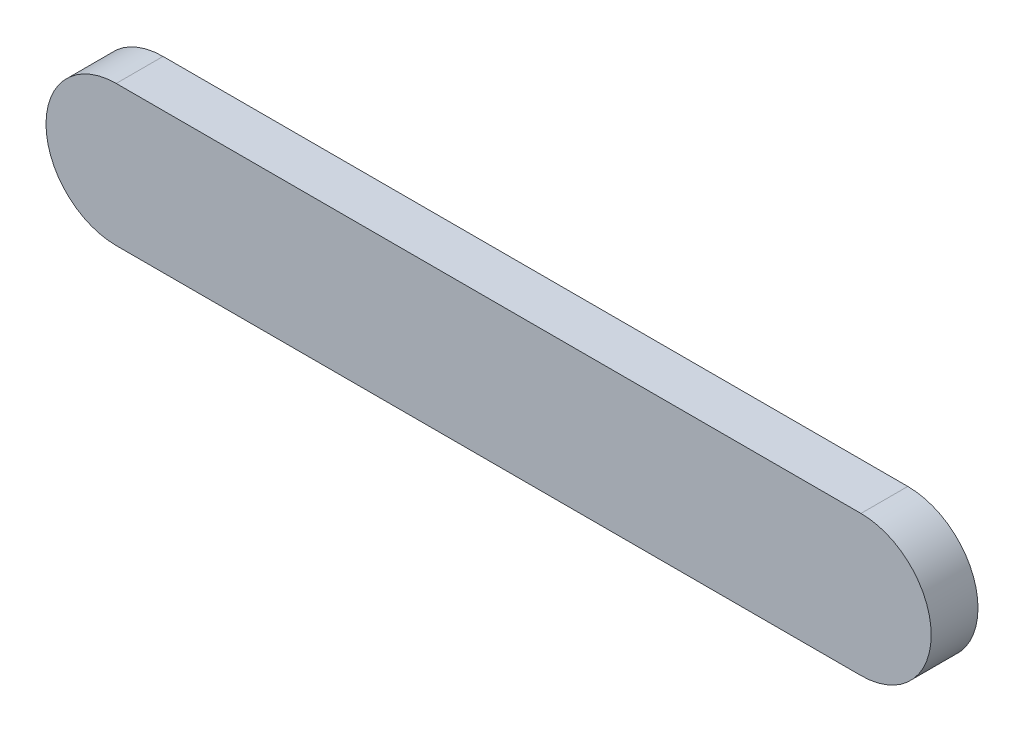
SolidWorks part; units mm, degrees
ref_plane "前视基准面" through (0, 0, 0) normal (0, 0, 1) x (1, 0, 0)
ref_plane "上视基准面" through (0, 0, 0) normal (0, 1, 0) x (1, 0, 0)
ref_plane "右视基准面" through (0, 0, 0) normal (1, 0, 0) x (0, 0, -1)
sketch "草图1" plane through (0, 0, 0) normal (0, 0, 1) x (1, 0, 0)
  line L3 (159.099, 30) -> (-159.099, 30)
  line L4 (-159.099, -30) -> (159.099, -30)
  arc A2 (-159.099, 30) -> (-159.099, -30) centre (-159.099, 0) ccw
  arc A3 (159.099, 30) -> (159.099, -30) centre (159.099, 0) cw
  point P6 (0, -30)
extrude "凸台-拉伸1" add sketch "草图1" along normal blind 10 and the other way blind 10
